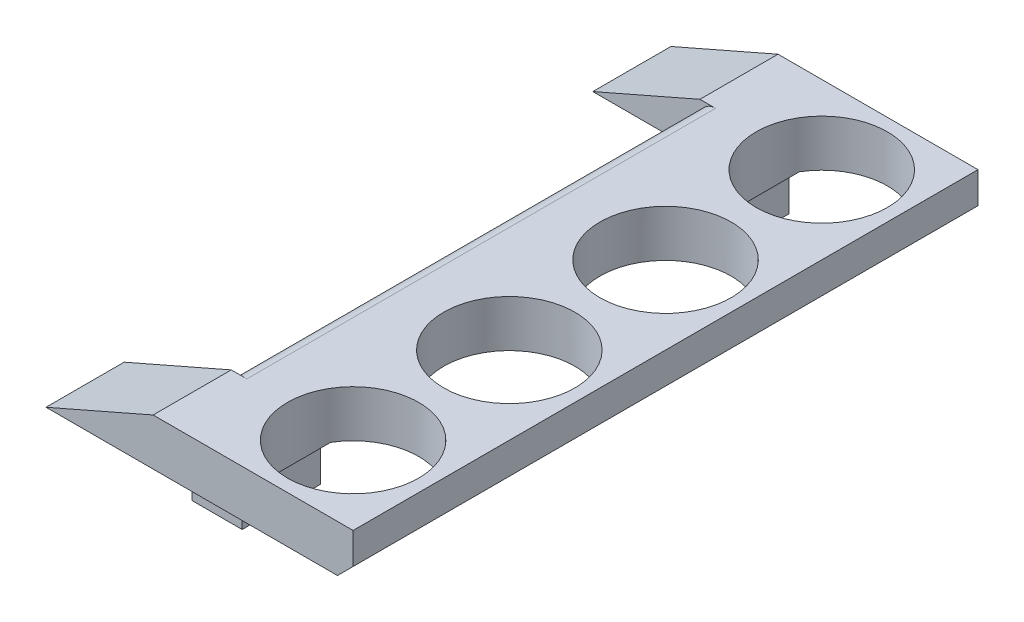
SolidWorks part; units mm, degrees
ref_plane "Спереди" through (0, 0, 0) normal (0, 0, 1) x (1, 0, 0)
ref_plane "Сверху" through (0, 0, 0) normal (0, 1, 0) x (1, 0, 0)
ref_plane "Справа" through (0, 0, 0) normal (1, 0, 0) x (0, 0, -1)
sketch "Эскиз3" plane through (0, 0, 0) normal (0, 1, 0) x (1, 0, 0)
  line L0 (-32, 100) -> (-32, 75)
  line L1 (-32, -100) -> (32, -100)
  line L2 (-32, -75) -> (-32, 75)
  line L3 (-32, 100) -> (32, 100)
  line L4 (32, -100) -> (32, 100)
  line L5 (-32, -75) -> (-32, -100)
  line L11 (-32, 100) -> (-67, 100)
  line L13 (-32, 75) -> (-67, 75)
  line L14 (-67, 100) -> (-67, 75)
  line L15 (-32, -100) -> (-67, -100)
  line L17 (-32, -75) -> (-67, -75)
  line L18 (-67, -100) -> (-67, -75)
  point P0 (0, 0)
  dimension "D1" = 64
  dimension "D2" = 200
  dimension "D3" = 35
  dimension "D4" = 25
  dimension "D5" = 25
  dimension "D6" = 35
  dimension "D7" = 32
  dimension "D8" = 100
extrude "Бобышка-Вытянуть1" add sketch "Эскиз3" along normal blind 15 contours L2 L5 L1 L4 L3 L0 region at (0, 0, 0)
extrude "Бобышка-Вытянуть2" add sketch "Эскиз3<3>" along normal blind 15 contours L11 L14 L13 L0 | L18 L15 L5 L17 region at (-49.5, 0, -87.5) region at (-49.5, 0, 87.5)
sketch "Эскиз3<3>" plane through (0, 0, 0) normal (0, 1, 0) x (1, 0, 0) same geometry as "Эскиз3"
ref_plane "Плоскость4" through (0, 0, 110) normal (0, 0, 1) x (1, 0, 0)
sketch "Эскиз6" plane through (0, 0, 110) normal (0, 0, 1) x (1, 0, 0)
  line L1 (-67, 15) -> (-32, 15)
  line L2 (-67, 15) -> (-67, -0.3126)
  line L5 (-32, 15) -> (-67, -0.3126)
  dimension "D1" = 23.63
  dimension "D2" = 35
  dimension "D3" = 15.3126
extrude "Вырез-Вытянуть1" cut sketch "Эскиз6" against normal blind 245
ref_plane "Плоскость5" through (0, 15, 0) normal (0, 1, 0) x (1, 0, 0)
sketch "Эскиз7" plane through (0, 15, 0) normal (0, 1, 0) x (1, 0, 0)
  line L0 (32, -100) -> (32, 100) construction
  line L1 (-32, 100) -> (32, 100) construction
  line L2 (-32, -100) -> (32, -100) construction
  circle A0 centre (7, 75) radius 21
  circle A1 centre (7, 25) radius 21
  circle A2 centre (7, -25) radius 21
  circle A3 centre (7, -75) radius 21
  point P16 (32, -79.7783)
  dimension "D1" = 42
  dimension "D2" = 25
  dimension "D3" = 25
  dimension "D5" = 25
  dimension "D4" = 4
extrude "Вырез-Вытянуть2" cut sketch "Эскиз7" against normal blind 15 contours A0 | A1 | A2 | A3
ref_plane "Плоскость6" through (0, 0, 0) normal (0, -1, 0) x (-1, 0, 0)
sketch "Эскиз8" plane through (0, 0, 0) normal (0, -1, 0) x (-1, 0, 0)
  line L0 (-28, -75) -> (43.4249, -75) construction
  line L1 (32, -75) -> (66.2855, -75) construction
  line L2 (32, -75) -> (32, 75) construction
  line L3 (0, 0) -> (-41.7473, 0) construction
  line L4 (32, -100) -> (32, 100) construction
  line L6 (32, 62.5) -> (16, 62.5)
  line L7 (32, -87.5) -> (16, -87.5)
  line L8 (32, -87.5) -> (32, -62.5)
  line L9 (32, -62.5) -> (16, -62.5)
  line L10 (16, -87.5) -> (16, -62.5)
  line L11 (16, 87.5) -> (16, 62.5)
  line L12 (32, 87.5) -> (16, 87.5)
  line L13 (32, 87.5) -> (32, 62.5)
  circle A0 centre (-7, -75) radius 21 construction
  circle A1 centre (23, -75) radius 5
  circle A2 centre (23, 75) radius 5
  point P8 (-7, -75)
  point P21 (32, -75)
  point P22 (32, 75)
  point P23 (32, -87.5)
  point P26 (32, 87.5)
  dimension "D1" = 10
  dimension "D2" = 30
  dimension "D3" = 9
  dimension "D4" = 12.5
  dimension "D5" = 12.5
  dimension "D6" = 16
  dimension "D7" = 25
extrude "Вырез-Вытянуть4" cut sketch "Эскиз8" against normal blind 10 contours A2 | A1 region at (-23, 0, -75)
extrude "Бобышка-Вытянуть4" add sketch "Эскиз8<5>" along normal blind 15
sketch "Эскиз8<5>" plane through (0, 0, 0) normal (0, -1, 0) x (-1, 0, 0) same geometry as "Эскиз8"
chamfer "Фаска1" distance 5 angle 45 1 edges at (32, 0, 0)
fillet "Скругление1" radius 5 1 edges at (-32, 15, 0) type face fillet first side face at (7, 15, -54) second side face at (-32, -2.5, 0)
chamfer "Фаска2" distance 5 angle 45 2 edges at (-16, 0, -75) (-16, 0, 75)
